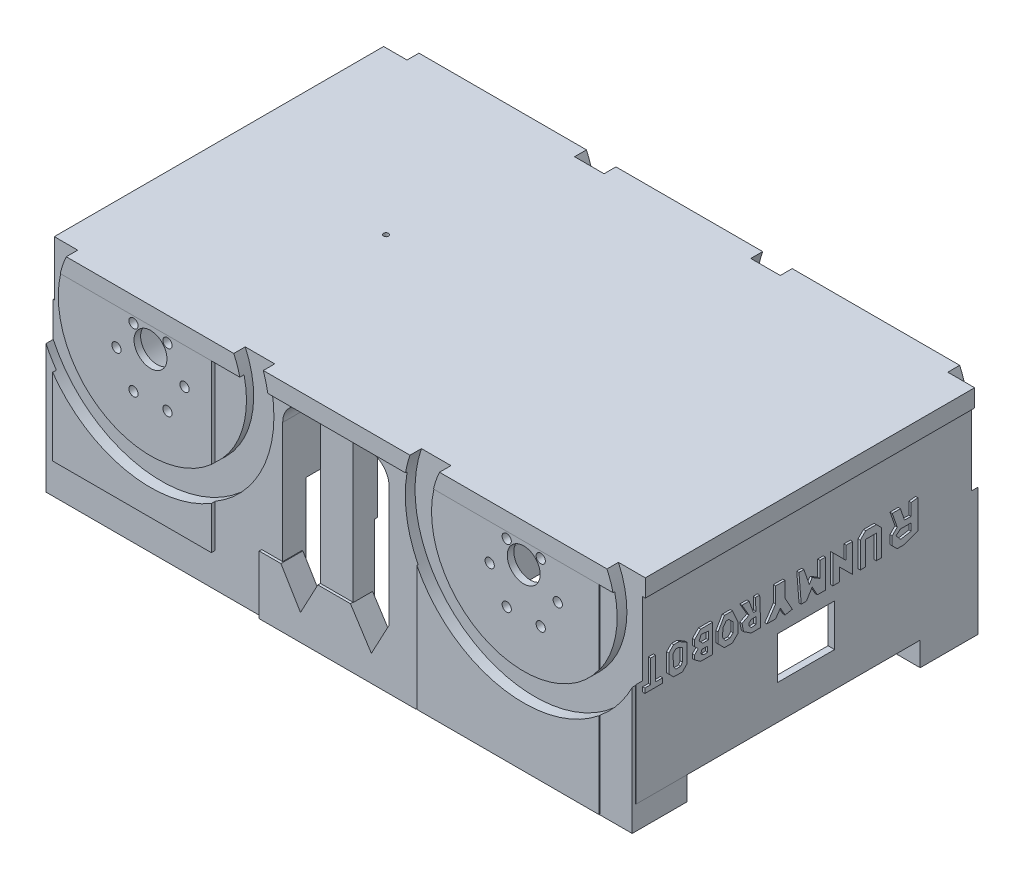
SolidWorks part; units mm, degrees
ref_plane "Front Plane" through (0, 0, 0) normal (0, 0, 1) x (1, 0, 0)
ref_plane "Top Plane" through (0, 0, 0) normal (0, 1, 0) x (1, 0, 0)
ref_plane "Right Plane" through (0, 0, 0) normal (1, 0, 0) x (0, 0, -1)
sketch "MotorHoldersSketch" plane through (0, 0, 0) normal (0, 0, 1) x (1, 0, 0)
  line L0 (0, 0) -> (170, 0) construction
  line L1 (0, 0) -> (0, 23.41) construction
  line L2 (170, 0) -> (170, 23.41) construction
  circle A0 centre (0, 0) radius 23.41
  circle A1 centre (170, 0) radius 23.41
ref_axis "MotorCenterAxis1" through (0, 0, 0) along (0, 0, 1)
ref_axis "MotorCenterAxis2" through (170, 0, 0) along (0, 0, 1)
extrude "MotorHolders" add sketch "MotorHoldersSketch" along normal blind 80 and the other way blind 80
sketch "Sketch3" plane through (0, 0, 0) normal (0, 0, 1) x (1, 0, 0)
  line L1 (1.9406, 21.133) -> (168.3435, 21.133)
  line L2 (1.9406, 21.133) -> (1.9406, 18.3155)
  line L3 (1.9406, 18.3155) -> (168.3435, 18.3155)
  line L4 (168.3435, 21.133) -> (168.3435, 18.3155)
sketch "Sketch4" plane through (0, 0, 0) normal (0, 1, 0) x (1, 0, 0)
  line L1 (221.2811, -76.3794) -> (-41.4939, -76.3794)
  line L2 (221.2811, -76.3794) -> (221.2811, 76.7331)
  line L3 (221.2811, 76.7331) -> (-41.4939, 76.7331)
  line L4 (-41.4939, -76.3794) -> (-41.4939, 76.7331)
extrude "Cut-Extrude1" cut sketch "Sketch4" against normal blind 26
ref_axis "Axis3" through (170, 0, 0) along (0, -1, 0)
sketch3d "ReferencePlanePosition"
  line L0 (170, 0, 0) -> (170, -34.8293, 0)
  line L1 (170, 0, 0) -> (170, -38.994, 0) construction
ref_plane "ReferencePlane" through (170, -34.8293, 0) normal (0, -1, 0) x (-1, 0, 0)
sketch "Sketch6" plane through (170, -34.8293, 0) normal (0, -1, 0) x (-1, 0, 0)
  line L1 (219.5858, 78.949) -> (112.1002, 78.949)
  line L2 (219.5858, 78.949) -> (219.5858, 65.5282)
  line L3 (219.5858, 65.5282) -> (112.1002, 65.5282)
  line L4 (112.1002, 78.949) -> (112.1002, 65.5282)
  line L5 (219.3147, -40.0209) -> (111.499, -40.0209)
  line L6 (219.3147, -40.0209) -> (219.3147, -78.2822)
  line L7 (219.3147, -78.2822) -> (111.499, -78.2822)
  line L8 (111.499, -40.0209) -> (111.499, -78.2822)
  line L9 (61.4891, 77.8627) -> (19.9904, 77.8627)
  line L10 (61.4891, 77.8627) -> (61.4891, 40.7512)
  line L11 (61.4891, 40.7512) -> (19.9904, 40.7512)
  line L12 (19.9904, 77.8627) -> (19.9904, 40.7512)
  line L13 (61.8484, -44.1716) -> (20.0852, -44.1716)
  line L14 (61.8484, -44.1716) -> (61.8484, -79.4437)
  line L15 (61.8484, -79.4437) -> (20.0852, -79.4437)
  line L16 (20.0852, -44.1716) -> (20.0852, -79.4437)
  line L17 (213.765, 73.0364) -> (192.9548, 73.0364)
  line L18 (213.765, 73.0364) -> (213.765, 71.0153)
  line L19 (213.765, 71.0153) -> (192.9548, 71.0153)
  line L20 (192.9548, 73.0364) -> (192.9548, 71.0153)
  line L21 (41.3552, 69.1777) -> (28.5109, 69.1777)
  line L22 (41.3552, 69.1777) -> (41.3552, 50.8413)
  line L23 (41.3552, 50.8413) -> (28.5109, 50.8413)
  line L24 (28.5109, 69.1777) -> (28.5109, 50.8413)
  line L25 (43.3068, -72.8101) -> (32.1723, -72.8101)
  line L26 (43.3068, -72.8101) -> (43.3068, -54.7747)
  line L27 (43.3068, -54.7747) -> (32.1723, -54.7747)
  line L28 (32.1723, -72.8101) -> (32.1723, -54.7747)
  line L29 (211.9411, -70.4881) -> (201.0982, -70.4881)
  line L30 (211.9411, -70.4881) -> (211.9411, -60.1404)
  line L31 (211.9411, -60.1404) -> (201.0982, -60.1404)
  line L32 (201.0982, -70.4881) -> (201.0982, -60.1404)
  line L33 (97.1795, 78.949) -> (79.4162, 78.949)
  line L34 (97.1795, 78.949) -> (97.1795, 67.7632)
  line L35 (97.1795, 67.7632) -> (79.4162, 67.7632)
  line L36 (79.4162, 78.949) -> (79.4162, 67.7632)
  line L37 (58.6711, 51.3198) -> (53.8697, 51.3198)
  line L38 (58.6711, 51.3198) -> (58.6711, 67.7632)
  line L39 (58.6711, 67.7632) -> (53.8697, 67.7632)
  line L40 (53.8697, 51.3198) -> (53.8697, 67.7632)
  line L41 (94.2281, -78.2822) -> (79.4162, -78.2822)
  line L42 (94.2281, -78.2822) -> (94.2281, -67.2515)
  line L43 (94.2281, -67.2515) -> (79.4162, -67.2515)
  line L44 (79.4162, -78.2822) -> (79.4162, -67.2515)
  line L45 (56.3648, -69.8638) -> (51.7107, -69.8638)
  line L46 (56.3648, -69.8638) -> (56.3648, -55.4273)
  line L47 (56.3648, -55.4273) -> (51.7107, -55.4273)
  line L48 (51.7107, -69.8638) -> (51.7107, -55.4273)
  line L49 (-20.7001, -79.4437) -> (-48.8506, -79.4437)
  line L50 (-20.7001, -79.4437) -> (-20.7001, -54.5097)
  line L51 (-20.7001, -54.5097) -> (-48.8506, -54.5097)
  line L52 (-48.8506, -79.4437) -> (-48.8506, -54.5097)
  line L53 (-18.3873, 77.8627) -> (-49.0581, 77.8627)
  line L54 (-18.3873, 77.8627) -> (-18.3873, 51.5325)
  line L55 (-18.3873, 51.5325) -> (-49.0581, 51.5325)
  line L56 (-49.0581, 77.8627) -> (-49.0581, 51.5325)
  line L57 (-41.8141, -72.8101) -> (-31.6362, -72.8101)
  line L58 (-41.8141, -72.8101) -> (-41.8141, -62.9794)
  line L59 (-41.8141, -62.9794) -> (-31.6362, -62.9794)
  line L60 (-31.6362, -72.8101) -> (-31.6362, -62.9794)
  line L61 (-31.6362, 69.1777) -> (-41.5347, 69.1777)
  line L62 (-31.6362, 69.1777) -> (-31.6362, 58.5421)
  line L63 (-31.6362, 58.5421) -> (-41.5347, 58.5421)
  line L64 (-41.5347, 69.1777) -> (-41.5347, 58.5421)
extrude "PowerBankHolders" add sketch "Sketch6" along normal blind 40 and the other way blind 59 separate body
sketch3d "3DSketch3"
  line L0 (170, 0, 0) -> (170, -64.5, 0) construction
ref_plane "Plane2" through (170, -64.5, 0) normal (0, -1, 0) x (-1, 0, 0)
sketch "Sketch7" plane through (170, -64.5, 0) normal (0, -1, 0) x (-1, 0, 0)
  line L1 (-9.5047, -80.801) -> (181.32, -80.801)
  line L2 (-9.5047, -80.801) -> (-9.5047, 73.8662)
  line L3 (-9.5047, 73.8662) -> (181.32, 73.8662)
  line L4 (181.32, -80.801) -> (181.32, 73.8662)
  line L5 (151.8712, -54.3972) -> (26.5361, -54.3972)
  line L6 (151.8712, -54.3972) -> (151.8712, 46.2413)
  line L7 (151.8712, 46.2413) -> (26.5361, 46.2413)
  line L8 (26.5361, -54.3972) -> (26.5361, 46.2413)
ref_point "Point1"
ref_point "Point2"
sketch3d "3DSketch11"
  line L0 (0, 0, -80) -> (170, 0, 80) construction
  point P4 (85, 0, 0)
sketch "MotorHolderExtrudeSketch" plane through (0, 0, 0) normal (0, 0, 1) x (1, 0, 0)
  circle A0 centre (170, 0) radius 20.415
  circle A1 centre (0, 0) radius 20.415
  circle A3 centre (0, 0) radius 23.41 construction
  circle A4 centre (170, 0) radius 23.41 construction
ref_point "TopOfMotors"
ref_plane "TangentToTopOfMotors" through (0, -20.415, 0) normal (0, 1, 0) x (1, 0, 0)
ref_axis "Axis4" through (85, 0, 0) along (0, -1, 0)
ref_plane "BottomOfPowerBankRegion" through (0, -20.425, 0) normal (0, 1, 0) x (1, 0, 0)
ref_point "CenterAtBottomOfPowerBank"
ref_plane "TopOfPowerBankPlane" through (0, -54.425, 0) normal (0, 1, 0) x (1, 0, 0)
sketch "Sketch13" plane through (0, -54.425, 0) normal (0, 1, 0) x (1, 0, 0)
  line L1 (-19.4498, 72.5454) -> (166.1636, 72.5454)
  line L2 (-19.4498, 72.5454) -> (-19.4498, -78.2051)
  line L3 (-19.4498, -78.2051) -> (166.1636, -78.2051)
  line L4 (166.1636, 72.5454) -> (166.1636, -78.2051)
  line L5 (19.3173, -49.583) -> (137.9607, -49.583)
  line L6 (19.3173, -49.583) -> (19.3173, -21.0549)
  line L7 (19.3173, -21.0549) -> (137.9607, -21.0549)
  line L8 (137.9607, -49.583) -> (137.9607, -21.0549)
  line L9 (19.3173, 56.6778) -> (137.9607, 56.6778)
  line L10 (19.3173, 56.6778) -> (19.3173, 36.3234)
  line L11 (19.3173, 36.3234) -> (137.9607, 36.3234)
  line L12 (137.9607, 56.6778) -> (137.9607, 36.3234)
  line L13 (19.3173, 18.3186) -> (137.9607, 18.3186)
  line L14 (19.3173, 18.3186) -> (19.3173, -7.3615)
  line L15 (19.3173, -7.3615) -> (137.9607, -7.3615)
  line L16 (137.9607, 18.3186) -> (137.9607, -7.3615)
sketch "Sketch15" plane through (150.0096, 0, 0) normal (1, 0, 0) x (0, 0, -1)
  line L1 (72.5313, -25.7765) -> (45.7099, -25.7765)
  line L2 (72.5313, -25.7765) -> (72.5313, -24.2242)
  line L3 (72.5313, -24.2242) -> (45.7099, -24.2242)
  line L4 (45.7099, -25.7765) -> (45.7099, -24.2242)
ref_plane "Plane6" through (0, 0, 0) normal (0, 0, 1) x (1, 0, 0)
sketch "MotorGeometry1" plane through (0, 0, 0) normal (0, 0, 1) x (1, 0, 0)
  line L0 (170, 0) -> (170, -13.42)
  line L1 (170, 0) -> (170, -34.8293) construction
  line L2 (170, -13.42) -> (162.25, -13.42) construction
  line L3 (170, -13.42) -> (177.75, -13.42) construction
  line L4 (170, -13.42) -> (170, 7) construction
  line L5 (170, 0) -> (185.5, 0) construction
  line L6 (170, 0) -> (154.5, 0) construction
  line L7 (170, 0) -> (170, 13.42) construction
  line L8 (170, 0) -> (170, 23.41) construction
  line L9 (170, 13.42) -> (177.75, 13.42) construction
  line L10 (170, 13.42) -> (162.25, 13.42)
ref_axis "BoltAxisA" through (185.5, 0, 0) along (0, 0, 1)
ref_axis "BoltAxisB" through (177.75, -13.42, 0) along (0, 0, 1)
ref_axis "BoltAxisC" through (162.25, -13.42, 0) along (0, 0, 1)
ref_axis "BoltAxisD" through (154.5, 0, 0) along (0, 0, 1)
ref_axis "BoltAxisE" through (162.25, 13.42, 0) along (0, 0, 1)
ref_axis "BoltAxisF" through (177.75, 13.42, 0) along (0, 0, 1)
ref_point "Point6"
ref_point "Point7"
ref_point "Point8"
ref_point "Point9"
ref_point "Point10"
ref_point "Point11"
ref_point "Point12"
ref_point "Point13"
ref_point "Point14"
ref_point "Point15"
ref_point "Point16"
ref_point "Point17"
ref_plane "Plane7" through (0, 0, 0) normal (0, 0, 1) x (1, 0, 0)
sketch "MotorGeometry2" plane through (0, 0, 0) normal (0, 0, 1) x (1, 0, 0)
  line L0 (0, 0) -> (0, -13.42) construction
  line L1 (0, -13.42) -> (7.75, -13.42) construction
  line L2 (0, -13.42) -> (-7.75, -13.42) construction
  line L3 (0, 0) -> (0, 13.42)
  line L4 (0, -13.42) -> (0, 7) construction
  line L5 (0, 13.42) -> (7.75, 13.42) construction
  line L6 (0, 13.42) -> (-7.75, 13.42) construction
  line L7 (0, 0) -> (15.5, 0) construction
  line L8 (0, 0) -> (-15.5, 0) construction
  line L9 (0, 0) -> (0, 23.41) construction
ref_axis "Axis11" through (15.5, 0, 0) along (0, 0, 1)
ref_axis "Axis12" through (7.75, 13.42, 0) along (0, 0, 1)
ref_axis "Axis13" through (-7.75, 13.42, 0) along (0, 0, 1)
ref_axis "Axis14" through (-15.5, 0, 0) along (0, 0, 1)
ref_axis "Axis15" through (-7.75, -13.42, 0) along (0, 0, 1)
ref_axis "Axis16" through (7.75, -13.42, 0) along (0, 0, 1)
ref_point "Point18"
ref_point "Point19"
ref_point "Point20"
ref_point "Point21"
ref_point "Point22"
ref_point "Point23"
ref_point "Point24"
ref_point "Point25"
ref_point "Point26"
ref_point "Point27"
ref_point "Point28"
ref_point "Point29"
ref_plane "BottomPlane" through (0, 19.575, 0) normal (0, 1, 0) x (1, 0, 0)
ref_axis "OutputShaftReference1" through (0, 7, 0) along (0, 0, 1)
ref_point "Point35"
ref_axis "OutputShaftReference2" through (170, 7, 0) along (0, 0, 1)
sketch "Sketch21" plane through (0, 19.575, 0) normal (0, 1, 0) x (1, 0, 0)
  line L0 (219.6842, -79.5488) -> (-50.341, -79.5488) construction
  line L1 (-50.341, -79.5488) -> (-50.341, 79.7899) construction
  line L2 (-50.341, 79.7899) -> (219.6842, 79.7899) construction
  line L3 (219.6842, 79.7899) -> (219.6842, -79.5488) construction
  circle A0 centre (85, 0) radius 156.3953
extrude "BottomPlate" add sketch "Sketch21" along normal blind 5 and the other way blind 3
ref_plane "HoleReferencePlane1" through (0, 0, 80) normal (0, 0, 1) x (1, 0, 0)
ref_point "OutputShaftPosition3"
ref_point "OutputShaftPosition1"
sketch "Sketch23" plane through (0, 0, 80) normal (0, 0, 1) x (1, 0, 0)
  line L1 (27.7411, -59.3229) -> (-44.5901, -59.3229)
  line L2 (27.7411, -59.3229) -> (27.7411, 21.8402)
  line L3 (27.7411, 21.8402) -> (-44.5901, 21.8402)
  line L4 (-44.5901, -59.3229) -> (-44.5901, 21.8402)
  line L5 (121.3218, 21.8402) -> (204.258, 21.8402)
  line L6 (121.3218, 21.8402) -> (121.3218, -74.371)
  line L7 (121.3218, -74.371) -> (204.258, -74.371)
  line L8 (204.258, 21.8402) -> (204.258, -74.371)
extrude "MotorMountingSupport1" add sketch "Sketch23" against normal blind 6
ref_plane "HoleReferencePlane2" through (0, 0, -80) normal (0, 0, -1) x (-1, 0, 0)
ref_point "OutputShaftPosition4"
ref_point "OutputShaftPosition2"
sketch "Sketch24" plane through (0, 0, -80) normal (0, 0, -1) x (-1, 0, 0)
  line L1 (-202.1905, -75.2023) -> (-123.8485, -75.2023)
  line L2 (-202.1905, -75.2023) -> (-202.1905, 19.2374)
  line L3 (-202.1905, 19.2374) -> (-123.8485, 19.2374)
  line L4 (-123.8485, -75.2023) -> (-123.8485, 19.2374)
  line L5 (-24.3642, -64.1521) -> (29.5505, -64.1521)
  line L6 (-24.3642, -64.1521) -> (-24.3642, 22.5226)
  line L7 (-24.3642, 22.5226) -> (29.5505, 22.5226)
  line L8 (29.5505, -64.1521) -> (29.5505, 22.5226)
extrude "MotorMountingSuppor2" add sketch "Sketch24" against normal blind 6
sketch "Sketch17" plane through (0, 0, 80) normal (0, 0, 1) x (1, 0, 0)
  circle A0 centre (185.5, 0) radius 2.1
  circle A1 centre (177.75, -13.42) radius 2.1
  circle A2 centre (162.25, -13.42) radius 2.1
  circle A3 centre (154.5, 0) radius 2.1
  circle A4 centre (162.25, 13.42) radius 2.1
  circle A5 centre (177.75, 13.42) radius 2.1
  circle A6 centre (170, 7) radius 7.5
extrude "MotorHoles1" cut sketch "Sketch17" against normal blind 31.5
sketch "Sketch19" plane through (0, 0, -80) normal (0, 0, -1) x (-1, 0, 0)
  circle A0 centre (-185.5, 0) radius 2.1
  circle A1 centre (-177.75, -13.42) radius 2.1
  circle A2 centre (-162.25, -13.42) radius 2.1
  circle A3 centre (-154.5, 0) radius 2.1
  circle A4 centre (-162.25, 13.42) radius 2.1
  circle A5 centre (-177.75, 13.42) radius 2.1
  circle A6 centre (-170, 7) radius 7.5
sketch "BoltHolesSketch3" plane through (0, 0, 80) normal (0, 0, 1) x (1, 0, 0)
  circle A0 centre (7.75, -13.42) radius 2.1
  circle A1 centre (15.5, 0) radius 2.1
  circle A2 centre (7.75, 13.42) radius 2.1
  circle A3 centre (-7.75, 13.42) radius 2.1
  circle A4 centre (-15.5, 0) radius 2.1
  circle A5 centre (-7.75, -13.42) radius 2.1
  circle A6 centre (0, 7) radius 7.5
extrude "Cut-Extrude4" cut sketch "Sketch19" against normal blind 30
extrude "MotorHoles3" cut sketch "BoltHolesSketch3" against normal blind 31.5
sketch "BoltHolesSketch4" plane through (0, 0, -80) normal (0, 0, -1) x (-1, 0, 0)
  circle A0 centre (-15.5, 0) radius 2.1
  circle A1 centre (-7.75, 13.42) radius 2.1
  circle A2 centre (7.75, 13.42) radius 2.1
  circle A3 centre (15.5, 0) radius 2.1
  circle A4 centre (7.75, -13.42) radius 2.1
  circle A5 centre (-7.75, -13.42) radius 2.1
  circle A6 centre (0, 7) radius 7.5
extrude "MotorHoles4" cut sketch "BoltHolesSketch4" against normal blind 15
ref_plane "Front" through (219.0581, 0, 0) normal (1, 0, 0) x (0, 0, -1)
sketch "Sketch29" plane through (219.0581, 0, 0) normal (1, 0, 0) x (0, 0, -1)
  line L1 (76.6955, -63.9254) -> (-77.9397, -63.9254)
  line L2 (76.6955, -63.9254) -> (76.6955, 20.2062)
  line L3 (76.6955, 20.2062) -> (-77.9397, 20.2062)
  line L4 (-77.9397, -63.9254) -> (-77.9397, 20.2062)
  line L5 (-13.4507, -48.1531) -> (12.5493, -48.1531)
  line L6 (-13.4507, -48.1531) -> (-13.4507, -28.9404)
  line L7 (-13.4507, -28.9404) -> (12.5493, -28.9404)
  line L8 (12.5493, -48.1531) -> (12.5493, -28.9404)
extrude "Boss-Extrude8" add sketch "Sketch29" against normal blind 3
ref_plane "RaspberryPiBasePlane" through (0, 16.575, 0) normal (0, -1, 0) x (-1, 0, 0)
sketch "Sketch27" plane through (0, 16.575, 0) normal (0, -1, 0) x (-1, 0, 0)
  line L1 (31.6337, 64.5517) -> (-194.8264, 64.5517)
  line L2 (31.6337, 64.5517) -> (31.6337, -65.4335)
  line L3 (31.6337, -65.4335) -> (-194.8264, -65.4335)
  line L4 (-194.8264, 64.5517) -> (-194.8264, -65.4335)
extrude "Boss-Extrude6" add sketch "Sketch27" against normal blind 3
ref_plane "Plane12" through (0, -74.8293, 0) normal (0, -1, 0) x (-1, 0, 0)
sketch "Sketch28" plane through (0, -74.8293, 0) normal (0, -1, 0) x (-1, 0, 0)
  line L1 (-189.3897, -97.3973) -> (-123.0026, -97.3973)
  line L2 (-189.3897, -97.3973) -> (-189.3897, 96.7192)
  line L3 (-189.3897, 96.7192) -> (-123.0026, 96.7192)
  line L4 (-123.0026, -97.3973) -> (-123.0026, 96.7192)
sketch "Sketch40" plane through (0, 16.575, 0) normal (0, -1, 0) x (1, 0, 0)
  line L1 (-49.5858, -65.5282) -> (-15.7443, -65.5282)
  line L2 (-49.5858, -65.5282) -> (-49.5858, -33.9964)
  line L3 (-49.5858, -33.9964) -> (-15.7443, -33.9964)
  line L4 (-15.7443, -65.5282) -> (-15.7443, -33.9964)
extrude "Boss-Extrude11" add sketch "Sketch40" along normal blind 40
fillet "Fillet2" radius 15 1 edges at (-33.0588, 16.575, -33.9964) type face fillet first side face at (-28.7089, -2.1691, -33.9964) second side face at (85, 16.575, 156.3953)
fillet "Fillet3" radius 15 1 edges at (-32.6651, -23.425, -65.5282) type face fillet first side face at (-5.65, -13.42, -65.5282) second side face at (-32.6651, -23.425, -49.7623)
sketch "Sketch11" plane through (0, -20.425, 0) normal (0, 1, 0) x (1, 0, 0)
  line L0 (-34.2162, 4.2922) -> (204.2162, -4.2922) construction
  line L5 (-34.2162, -64.7581) -> (-34.2162, 73.3425)
  line L6 (204.2162, 63.611) -> (204.2162, -72.1954)
  line L7 (204.2162, -72.1954) -> (-34.2162, -64.7581)
  line L8 (204.2162, 63.611) -> (-34.2162, 73.3425)
  circle A0 centre (85, 0) radius 104 construction
extrude "PowerBankCut" cut sketch "Sketch11" against normal up to surface (54.4043 mm away) up to face at (204.7754, -74.8293, 66.9767)
extrude "MotorHolderCut" cut sketch "MotorHolderExtrudeSketch" against normal blind 77 and the other way blind 77
sketch "Sketch31" plane through (219.0581, 0, 0) normal (1, 0, 0) x (0, 0, -1)
  line L0 (49.4417, -6.1927) -> (49.4417, -19.3739)
  line L1 (49.4417, -19.3739) -> (42.9342, -21.6341)
  line L2 (42.9342, -21.6341) -> (40.0618, -21.6341)
  line L3 (40.0618, -21.6341) -> (37.7863, -19.3586)
  line L4 (37.7863, -19.3586) -> (37.7863, -15.3813)
  line L5 (37.7863, -15.3813) -> (40.0618, -13.1059)
  line L6 (40.0618, -13.1059) -> (37.7863, -6.5545)
  line L7 (37.7863, -6.5545) -> (41.498, -6.5545)
  line L8 (41.498, -6.5545) -> (43.4004, -12.0319)
  line L9 (43.4004, -12.0319) -> (46.389, -12.0319)
  line L10 (46.389, -12.0319) -> (46.389, -6.5545)
  line L11 (46.389, -6.5545) -> (49.4417, -6.1927)
  line L12 (33.0193, -21.6341) -> (33.0193, -9.8302)
  line L13 (33.0193, -9.8302) -> (30.5402, -7.3511)
  line L14 (30.5402, -7.3511) -> (25.7203, -7.3511)
  line L15 (25.7203, -7.3511) -> (23.2412, -9.8302)
  line L16 (23.2412, -9.8302) -> (23.2412, -21.6341)
  line L17 (23.2412, -21.6341) -> (25.7203, -21.6341)
  line L18 (25.7203, -21.6341) -> (25.7203, -10.7454)
  line L19 (25.7203, -10.7454) -> (30.5402, -10.7454)
  line L20 (30.5402, -10.7454) -> (30.5402, -21.6341)
  line L21 (30.5402, -21.6341) -> (33.0193, -21.6341)
  line L22 (19.7226, -8.5907) -> (19.7226, -21.6341)
  line L23 (19.7226, -21.6341) -> (13.8207, -15.7322)
  line L24 (13.8207, -15.7322) -> (13.8207, -21.6341)
  line L25 (13.8207, -21.6341) -> (10.7708, -21.6341)
  line L26 (10.7708, -21.6341) -> (10.7708, -8.5907)
  line L27 (10.7708, -8.5907) -> (16.7716, -14.5915)
  line L28 (16.7716, -14.5915) -> (16.7716, -8.5907)
  line L29 (16.7716, -8.5907) -> (19.7226, -8.5907)
  line L30 (7.3891, -8.5907) -> (7.3891, -21.6341)
  line L31 (7.3891, -21.6341) -> (3.7282, -21.6341)
  line L32 (3.7282, -21.6341) -> (1.3209, -17.37)
  line L33 (1.3209, -17.37) -> (-1.2519, -21.6341)
  line L34 (-1.2519, -21.6341) -> (-3.6554, -21.6341)
  line L35 (-3.6554, -21.6341) -> (-4.6916, -8.5907)
  line L36 (-4.6916, -8.5907) -> (-2.4537, -8.5907)
  line L37 (-2.4537, -8.5907) -> (0.0345, -15.7545)
  line L38 (0.0345, -15.7545) -> (1.3209, -13.6224)
  line L39 (1.3209, -13.6224) -> (4.8544, -15.7545)
  line L40 (4.8544, -15.7545) -> (4.8544, -8.5907)
  line L41 (4.8544, -8.5907) -> (7.3891, -8.5907)
  line L42 (-7.6823, -21.6341) -> (-10.9875, -15.7545)
  line L43 (-10.9875, -15.7545) -> (-10.9875, -8.5907)
  line L44 (-10.9875, -8.5907) -> (-15.3102, -8.5907)
  line L45 (-15.3102, -8.5907) -> (-15.3102, -15.7545)
  line L46 (-15.3102, -15.7545) -> (-19.2695, -21.6341)
  line L47 (-19.2695, -21.6341) -> (-15.3102, -21.6341)
  line L48 (-15.3102, -21.6341) -> (-13.1489, -18.4245)
  line L49 (-13.1489, -18.4245) -> (-10.9875, -22.2693)
  line L50 (-10.9875, -22.2693) -> (-7.6823, -21.6341)
  line L51 (46.389, -17.8857) -> (46.389, -14.5915)
  line L52 (46.389, -14.5915) -> (41.498, -14.5915)
  line L53 (41.498, -14.5915) -> (39.5067, -16.2541)
  line L54 (39.5067, -16.2541) -> (41.5656, -18.7201)
  line L55 (41.5656, -18.7201) -> (46.389, -17.8857)
  line L56 (-22.571, -8.5907) -> (-22.0989, -21.6341)
  line L57 (-22.0989, -21.6341) -> (-26.4915, -21.6341)
  line L58 (-26.4915, -21.6341) -> (-29.9116, -19.3586)
  line L59 (-29.9116, -19.3586) -> (-30.636, -15.7545)
  line L60 (-30.636, -15.7545) -> (-27.4135, -14.1052)
  line L61 (-27.4135, -14.1052) -> (-30.636, -8.5907)
  line L62 (-30.636, -8.5907) -> (-27.4135, -8.5907)
  line L63 (-27.4135, -8.5907) -> (-25.3987, -14.1052)
  line L64 (-25.3987, -14.1052) -> (-24.2952, -14.1052)
  line L65 (-24.2952, -14.1052) -> (-24.4948, -8.5907)
  line L66 (-24.4948, -8.5907) -> (-22.571, -8.5907)
  line L67 (-35.0099, -8.5907) -> (-38.6395, -8.5907)
  line L68 (-38.6395, -8.5907) -> (-41.5241, -13.6224)
  line L69 (-41.5241, -13.6224) -> (-41.5241, -18.4245)
  line L70 (-41.5241, -18.4245) -> (-38.6395, -21.3091)
  line L71 (-38.6395, -21.3091) -> (-35.0099, -21.3091)
  line L72 (-35.0099, -21.3091) -> (-32.4978, -18.797)
  line L73 (-32.4978, -18.797) -> (-32.4978, -14.1052)
  line L74 (-32.4978, -14.1052) -> (-35.0099, -8.5907)
  line L75 (-44.0593, -21.3091) -> (-44.0593, -8.5907)
  line L76 (-44.0593, -8.5907) -> (-49.4499, -8.5907)
  line L77 (-49.4499, -8.5907) -> (-52.2269, -11.3677)
  line L78 (-52.2269, -11.3677) -> (-52.2269, -14.1052)
  line L79 (-52.2269, -14.1052) -> (-50.5777, -15.7545)
  line L80 (-50.5777, -15.7545) -> (-52.2269, -17.4037)
  line L81 (-52.2269, -17.4037) -> (-52.2269, -19.3586)
  line L82 (-52.2269, -19.3586) -> (-49.4499, -21.3091)
  line L83 (-49.4499, -21.3091) -> (-44.0593, -21.3091)
  line L84 (-57.7977, -21.3091) -> (-55.6011, -19.1125)
  line L85 (-55.6011, -19.1125) -> (-55.6011, -10.7454)
  line L86 (-55.6011, -10.7454) -> (-59.2637, -8.5907)
  line L87 (-59.2637, -8.5907) -> (-61.7818, -8.5907)
  line L88 (-61.7818, -8.5907) -> (-63.9365, -10.7454)
  line L89 (-63.9365, -10.7454) -> (-63.9365, -19.1125)
  line L90 (-63.9365, -19.1125) -> (-61.7818, -21.2672)
  line L91 (-61.7818, -21.2672) -> (-57.7977, -21.3091)
  line L92 (-66.7918, -21.2672) -> (-74.8705, -21.2672)
  line L93 (-74.8705, -21.2672) -> (-74.8705, -19.1125)
  line L94 (-74.8705, -19.1125) -> (-72.2665, -19.1125)
  line L95 (-72.2665, -19.1125) -> (-72.2665, -8.5907)
  line L96 (-72.2665, -8.5907) -> (-69.9977, -8.5907)
  line L97 (-69.9977, -8.5907) -> (-69.9977, -19.1125)
  line L98 (-69.9977, -19.1125) -> (-66.7918, -19.1125)
  line L99 (-66.7918, -19.1125) -> (-66.7918, -21.2672)
  line L100 (-36.1114, -18.797) -> (-34.7181, -17.4037)
  line L101 (-34.7181, -17.4037) -> (-34.7181, -13.1059)
  line L102 (-34.7181, -13.1059) -> (-36.6627, -11.1613)
  line L103 (-36.6627, -11.1613) -> (-37.8659, -11.1613)
  line L104 (-37.8659, -11.1613) -> (-39.3107, -13.1059)
  line L105 (-39.3107, -13.1059) -> (-39.5155, -16.8544)
  line L106 (-39.5155, -16.8544) -> (-38.25, -18.7201)
  line L107 (-38.25, -18.7201) -> (-36.1114, -18.797)
  line L108 (-46.2436, -16.8544) -> (-48.9032, -16.8544)
  line L109 (-48.9032, -16.8544) -> (-49.4499, -18.4245)
  line L110 (-49.4499, -18.4245) -> (-48.0836, -19.3586)
  line L111 (-48.0836, -19.3586) -> (-46.2436, -19.3586)
  line L112 (-46.2436, -19.3586) -> (-46.2436, -16.8544)
  line L113 (-45.9206, -14.5915) -> (-45.9206, -11.1613)
  line L114 (-45.9206, -11.1613) -> (-49.2105, -10.7454)
  line L115 (-49.2105, -10.7454) -> (-50.1756, -12.8764)
  line L116 (-50.1756, -12.8764) -> (-48.5891, -14.5915)
  line L117 (-48.5891, -14.5915) -> (-45.9206, -14.5915)
  line L118 (-58.5672, -18.7201) -> (-57.7977, -17.4037)
  line L119 (-57.7977, -17.4037) -> (-57.7977, -11.7636)
  line L120 (-57.7977, -11.7636) -> (-59.6573, -10.7454)
  line L121 (-59.6573, -10.7454) -> (-60.8144, -10.7454)
  line L122 (-60.8144, -10.7454) -> (-62.101, -12.0319)
  line L123 (-62.101, -12.0319) -> (-61.7818, -17.4037)
  line L124 (-61.7818, -17.4037) -> (-60.8144, -18.7201)
  line L125 (-60.8144, -18.7201) -> (-58.5672, -18.7201)
  line L126 (-24.2952, -19.3586) -> (-24.2952, -16.2541)
  line L127 (-24.2952, -16.2541) -> (-26.4915, -16.2541)
  line L128 (-26.4915, -16.2541) -> (-27.4135, -17.1761)
  line L129 (-27.4135, -17.1761) -> (-27.4135, -18.4245)
  line L130 (-27.4135, -18.4245) -> (-26.3339, -19.5041)
  line L131 (-26.3339, -19.5041) -> (-24.2952, -19.3586)
extrude "Label" add sketch "Sketch31" along normal blind 1
sketch "Sketch32" plane through (0, 19.575, 0) normal (0, 1, 0) x (1, 0, 0)
  line L1 (-48.8137, 80.4301) -> (220.392, 80.4301)
  line L2 (-48.8137, 80.4301) -> (-48.8137, -80.215)
  line L3 (-48.8137, -80.215) -> (220.392, -80.215)
  line L4 (220.392, 80.4301) -> (220.392, -80.215)
  line L5 (283.5566, -218.7268) -> (-136.4889, -218.7268)
  line L8 (-136.4889, -218.7268) -> (-136.4889, 206.3198)
  line L10 (283.5566, 206.3198) -> (283.5566, -218.7268)
  line L13 (283.5566, 206.3198) -> (-136.4889, 206.3198)
extrude "BaseDefiningCut" cut sketch "Sketch32" along normal blind 20 and the other way blind 20
sketch "Sketch39" plane through (0, 16.575, 0) normal (0, -1, 0) x (1, 0, 0)
  line L1 (-48.8137, -65.5282) -> (-16.0867, -65.5282)
  line L2 (-48.8137, -65.5282) -> (-48.8137, -46.28)
  line L3 (-48.8137, -46.28) -> (-16.0867, -46.28)
  line L4 (-16.0867, -65.5282) -> (-16.0867, -46.28)
sketch "Sketch35" plane through (0, 0, -80.4301) normal (0, 0, -1) x (-1, 0, 0)
  line L0 (69.0502, 16.3777) -> (-36.4474, 27.6206)
  line L1 (-36.4474, 27.6206) -> (71.6404, 26.1593)
  line L2 (69.0502, 16.3777) -> (71.6404, 26.1593)
  line L3 (-223.8844, 30.8145) -> (-223.8844, 17.5678)
  line L4 (-223.8844, 17.5678) -> (-116.0163, 30.8145)
  line L5 (-116.0163, 30.8145) -> (-223.8844, 30.8145)
sketch "Sketch36" plane through (-49.3147, 0, 0) normal (-1, 0, 0) x (0, 0, 1)
  line L0 (40.0209, -74.8293) -> (40.0209, -38.3689) construction
  line L1 (49.3822, -38.3689) -> (78.2822, -38.3689) construction
  line L2 (40.0209, -38.3689) -> (40.0209, -74.8293) construction
  line L3 (78.2822, -0.425) -> (78.2822, -74.8293) construction
  circle A1 centre (49.3822, -38.3689) radius 7.7902
extrude "Cut-Extrude6" cut sketch "Sketch36" against normal blind 40
sketch "Sketch37" plane through (0, -20.425, 0) normal (0, -1, 0) x (1, 0, 0)
  line L1 (144.416, -35.6729) -> (89.0759, -35.6729)
  line L2 (144.416, -35.6729) -> (144.416, -65.4438)
  line L3 (144.416, -65.4438) -> (89.0759, -65.4438)
  line L4 (89.0759, -35.6729) -> (89.0759, -65.4438)
extrude "Cut-Extrude7" cut sketch "Sketch37" against normal blind 36
sketch "Sketch38" plane through (0, 16.575, 0) normal (0, -1, 0) x (1, 0, 0)
  line L0 (25.9964, 80.215) -> (25.9964, -1.3165) construction
  line L1 (-48.8137, 80.215) -> (219.2574, 80.215) construction
  circle A0 centre (25.9964, -1.3165) radius 1.1452
extrude "Cut-Extrude8" cut sketch "Sketch38" against normal blind 10
sketch "Sketch41" plane through (0, 0, 80) normal (0, 0, 1) x (1, 0, 0)
  circle A0 centre (0, 7) radius 42
  circle A1 centre (0, 7) radius 54.5
extrude "SpaceForWheel1" cut sketch "Sketch41" against normal blind 5 and the other way blind 10
sketch "Sketch42" plane through (0, 0, 80) normal (0, 0, 1) x (1, 0, 0)
  circle A0 centre (170, 7) radius 42
  circle A1 centre (170, 7) radius 54.5
extrude "Cut-Extrude10" cut sketch "Sketch42" against normal blind 5 and the other way blind 10
sketch "Sketch43" plane through (0, 0, -80) normal (0, 0, -1) x (-1, 0, 0)
  circle A0 centre (-170, 7) radius 42
  circle A1 centre (-170, 7) radius 54.5
extrude "Cut-Extrude11" cut sketch "Sketch43" against normal blind 5 and the other way blind 10
sketch "Sketch44" plane through (0, 0, -80) normal (0, 0, -1) x (-1, 0, 0)
  circle A0 centre (0, 7) radius 42
  circle A1 centre (0, 7) radius 54.5
extrude "Cut-Extrude12" cut sketch "Sketch44" against normal blind 5 and the other way blind 10
sketch "Sketch45" plane through (-48.8137, 0, 0) normal (-1, 0, 0) x (0, 0, 1)
  line L0 (-75, 24.575) -> (75, 24.575) construction
  line L1 (-72.1063, 24.575) -> (42.0312, 24.575)
  line L2 (-72.1063, 24.575) -> (-72.1063, -74.1222)
  line L3 (-72.1063, -74.1222) -> (42.0312, -74.1222)
  line L4 (42.0312, 24.575) -> (42.0312, -74.1222)
extrude "BackPlate" add sketch "Sketch45" against normal blind 2
sketch "Sketch46" plane through (0, -74.8293, 0) normal (0, -1, 0) x (1, 0, 0)
  line L1 (97.1427, -74.9256) -> (213.5256, -74.9256)
  line L2 (97.1427, -74.9256) -> (97.1427, -71.5234)
  line L3 (97.1427, -71.5234) -> (213.5256, -71.5234)
  line L4 (213.5256, -74.9256) -> (213.5256, -71.5234)
  line L5 (97.1427, 72.8226) -> (213.5256, 72.8226)
  line L6 (97.1427, 72.8226) -> (97.1427, 77.4687)
  line L7 (97.1427, 77.4687) -> (213.5256, 77.4687)
  line L8 (213.5256, 72.8226) -> (213.5256, 77.4687)
fillet "Fillet8" radius 10 1 edges at (57.8998, 16.575, -72.2386) type face fillet first side face at (57.8998, -26.2264, -71.3533) second side face at (25.9964, 16.575, -2.4617)
fillet "Fillet9" radius 10 1 edges at (108.5109, 16.575, -59.3069) type face fillet first side face at (108.5109, -15.7761, -62.8937) second side face at (25.9964, 16.575, -2.4617)
fillet "Fillet10" radius 10 1 edges at (108.1516, 16.575, 61.8076) type face fillet first side face at (108.1516, -26.2264, 64.2714) second side face at (25.9964, 16.575, -2.4617)
sketch "Sketch49" plane through (0, 0, 80) normal (0, 0, 1) x (1, 0, 0)
  line L0 (27.7411, -24.5346) -> (27.7411, 16.575) construction
  circle A0 centre (27.7411, 12.953) radius 3.5831
fillet "Fillet11" radius 10 1 edges at (58.501, 16.575, 59.1515) type face fillet first side face at (58.501, -26.2264, 61.9844) second side face at (25.9964, 16.575, -2.4617)
sketch "Sketch50" plane through (0, -74.8293, 0) normal (0, -1, 0) x (1, 0, 0)
  line L1 (-49.3147, 40.0209) -> (-40.7689, 40.0209)
  line L2 (-49.3147, 40.0209) -> (-49.3147, 52.7795)
  line L3 (-49.3147, 52.7795) -> (-40.7689, 52.7795)
  line L4 (-40.7689, 40.0209) -> (-40.7689, 52.7795)
  line L5 (-49.5858, -65.5282) -> (-35.8777, -65.5282)
  line L6 (-49.5858, -65.5282) -> (-49.5858, -77.7316)
  line L7 (-49.5858, -77.7316) -> (-35.8777, -77.7316)
  line L8 (-35.8777, -65.5282) -> (-35.8777, -77.7316)
sketch "Sketch51" plane through (0, 0, 79.4437) normal (0, 0, 1) x (1, 0, 0)
  line L0 (108.1516, -47.9804) -> (100.047, -63.1792)
  line L1 (108.1516, 6.575) -> (108.1516, -74.8293) construction
  line L2 (100.047, -63.1792) -> (90.5163, -48.3368)
  line L3 (90.5163, -48.3368) -> (75.6762, -48.3368)
  line L4 (75.6762, -48.3368) -> (67.7615, -63.1792)
  line L5 (67.7615, -63.1792) -> (58.8398, -48.3368)
  line L6 (58.8398, -48.3368) -> (48.9291, -48.3368)
  line L7 (48.9291, -48.3368) -> (48.9291, -75.0407)
  line L8 (48.9291, -75.0407) -> (120.2514, -75.0407)
  line L9 (120.2514, -75.0407) -> (120.2514, -47.9804)
  line L10 (120.2514, -47.9804) -> (108.1516, -47.9804)
extrude "Boss-Extrude12" add sketch "Sketch51" against normal blind 10
sketch "Sketch53" plane through (0, 0, -77.8627) normal (0, 0, -1) x (-1, 0, 0)
  line L1 (-57.7992, -55.7616) -> (-64.6668, -65.1072)
  line L2 (-64.6668, -65.1072) -> (-72.7541, -55.7616)
  line L3 (-72.7541, -55.7616) -> (-90.6554, -55.7616)
  line L4 (-90.6554, -55.7616) -> (-98.6681, -65.1072)
  line L5 (-98.6681, -65.1072) -> (-108.5109, -55.7616)
  line L6 (-108.5109, 6.575) -> (-108.5109, -74.8293) construction
  line L7 (-108.5109, -55.7616) -> (-123.8485, -55.7616)
  line L8 (-123.8485, -21.9878) -> (-123.8485, -74.8293) construction
  line L9 (-123.8485, -55.7616) -> (-123.8485, -74.8293)
  line L10 (-123.8485, -74.8293) -> (-52.4383, -74.8293)
  line L11 (-52.4383, -74.8293) -> (-52.4383, -55.7616)
  line L12 (-52.4383, -55.7616) -> (-57.7992, -55.7616)
extrude "Boss-Extrude13" add sketch "Sketch53" against normal blind 9
